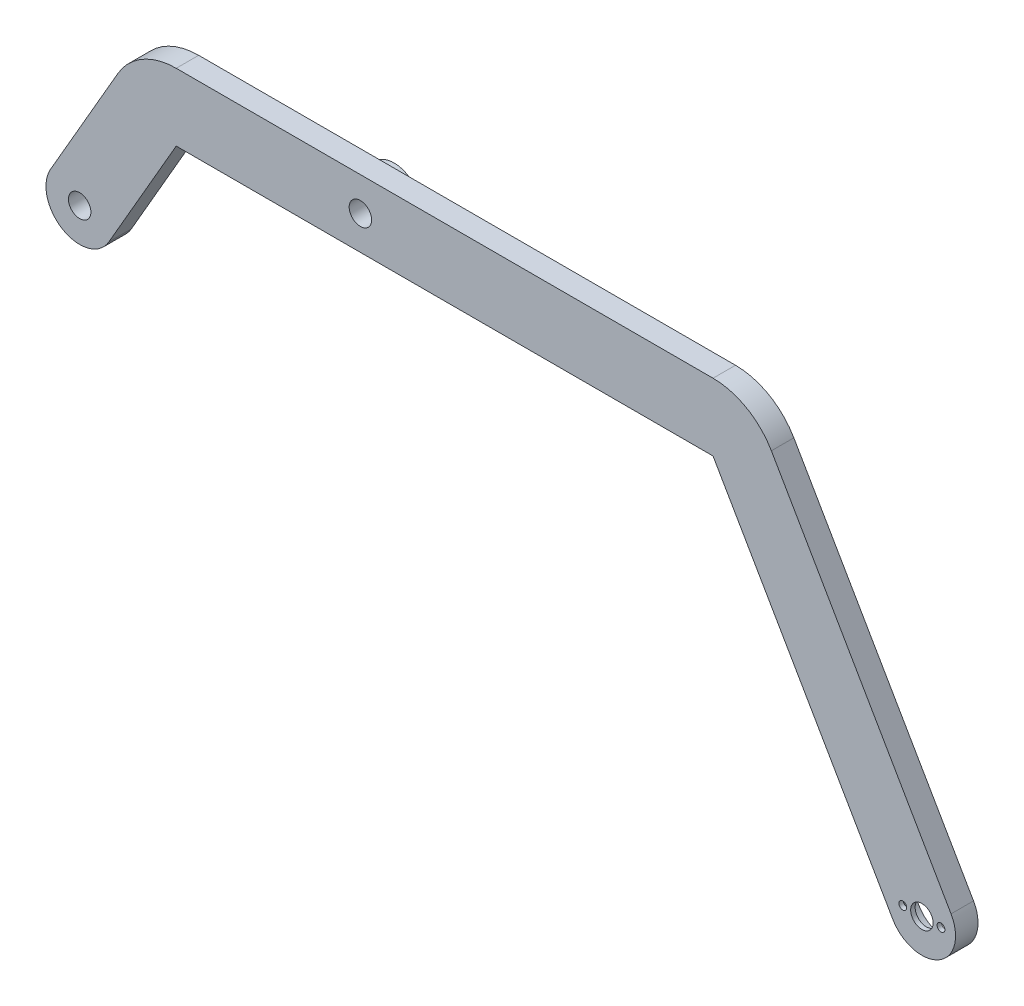
SolidWorks part; units mm, degrees
ref_plane "Front Plane" through (0, 0, 0) normal (0, 0, 1) x (1, 0, 0)
ref_plane "Top Plane" through (0, 0, 0) normal (0, 1, 0) x (1, 0, 0)
ref_plane "Right Plane" through (0, 0, 0) normal (1, 0, 0) x (0, 0, -1)
sketch "Sketch1" plane through (0, 0, 0) normal (0, 0, 1) x (1, 0, 0)
  line L0 (0, -15) -> (0, 15) construction
  line L4 (-82.0096, -15) -> (-112.0096, -66.9615)
  line L6 (-137.9904, -51.9615) -> (-107.9904, 0)
  line L7 (262.9904, -138.5641) -> (182.9904, 0)
  line L9 (157.0096, -15) -> (237.0096, -153.5641)
  line L10 (0, 15) -> (157.0096, 15)
  line L11 (0, -15) -> (157.0096, -15)
  line L12 (0, 15) -> (-82.0096, 15)
  line L13 (0, -15) -> (-82.0096, -15)
  line L14 (237.0096, -153.5641) -> (262.9904, -138.5641) construction
  line L15 (-137.9904, -51.9615) -> (-112.0096, -66.9615) construction
  arc A1 (-107.9904, 0) -> (-82.0096, 15) centre (-82.0096, -15) cw
  arc A2 (182.9904, 0) -> (157.0096, 15) centre (157.0096, -15) ccw
  arc A6 (237.0096, -153.5641) -> (262.9904, -138.5641) centre (250, -146.0641) ccw
  arc A7 (-137.9904, -51.9615) -> (-112.0096, -66.9615) centre (-125, -59.4615) ccw
  circle A8 centre (258.5, -146.0433) radius 1.75
  circle A9 centre (241.5, -146.0848) radius 1.75
  point P4 (0, 0)
  point P7 (0, -15)
  point P20 (0, 15)
  dimension "D2" = 60
  dimension "D6" = 3.5
  dimension "D7" = 3.5
  dimension "D1" = 30
  dimension "D3" = 250
  dimension "D4" = 160
  dimension "D5" = 125
extrude "Boss-Extrude1" add sketch "Sketch1" along normal blind 10
sketch "Sketch2" plane through (0, 0, 10) normal (0, 0, 1) x (1, 0, 0)
  circle A0 centre (-125, -59.4615) radius 5
  circle A1 centre (250, -146.0641) radius 5
  circle A2 centre (0, 0) radius 5
  dimension "D1" = 10
extrude "Cut-Extrude1" cut sketch "Sketch2" against normal up to surface (10 mm away) up to face at (260.25, -146.0433, 0)
sketch "Sketch3" plane through (0, 0, 0) normal (0, 0, -1) x (-1, 0, 0)
  circle A0 centre (0, 0) radius 12
extrude "Boss-Extrude2" add sketch "Sketch3" along normal blind 5
sketch "Sketch4" plane through (0, 0, 0) normal (0, 0, -1) x (-1, 0, 0)
  circle A0 centre (-250, -146.0641) radius 13
  dimension "D1" = 26
extrude "Cut-Extrude2" cut sketch "Sketch4" against normal offset from surface (8 mm away) 2 up to face at (-120, -59.4615, 10)
